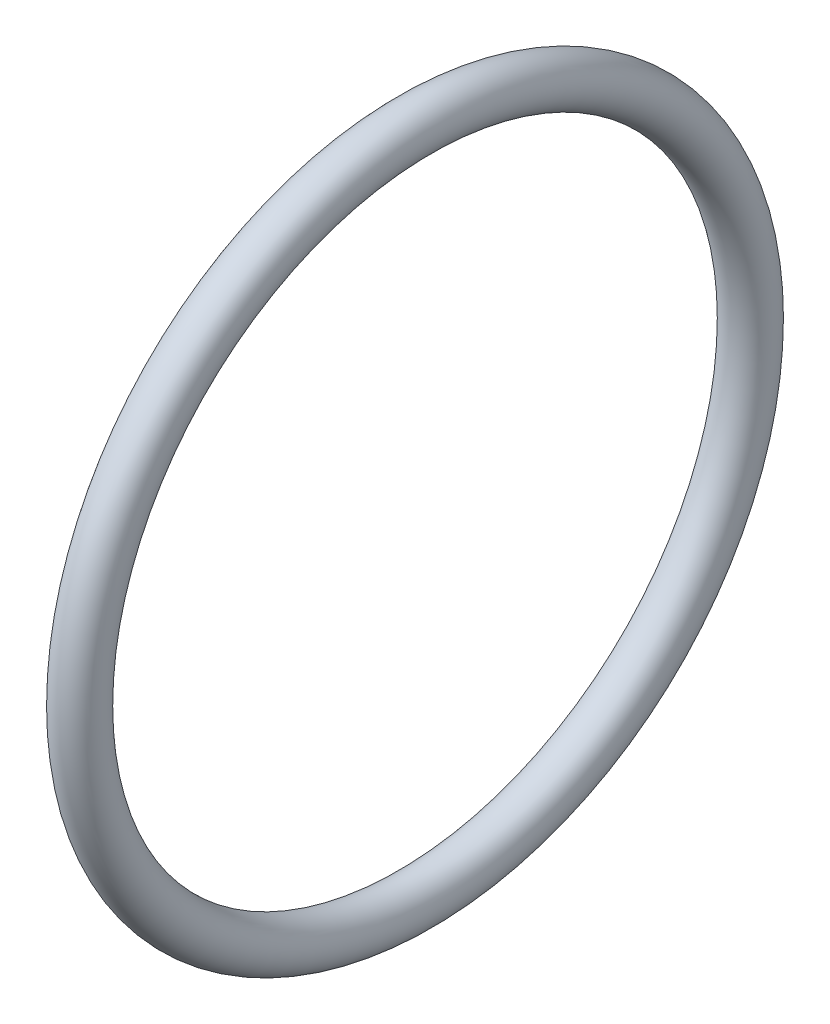
SolidWorks part; units mm, degrees
ref_plane "Front Plane" through (0, 0, 0) normal (0, 0, 1) x (1, 0, 0)
ref_plane "Top Plane" through (0, 0, 0) normal (0, 1, 0) x (1, 0, 0)
ref_plane "Right Plane" through (0, 0, 0) normal (1, 0, 0) x (0, 0, -1)
sketch "Sketch2" plane through (0, 0, 0) normal (0, 0, 1) x (1, 0, 0)
  line L0 (0, 0) -> (58.591, 0) construction
  line L2 (0, 0) -> (18.4, 0)
  line L3 (0, 0) -> (0, 2.5)
  line L4 (0, 2.5) -> (18.4, 2.5)
  line L5 (18.4, 0) -> (18.4, 2.5)
  line L6 (6.0094, 2.5) -> (6.0094, 6)
  line L11 (6.0094, 6) -> (9.9794, 6)
  line L16 (12.9794, 6) -> (12.9794, 3)
  line L17 (12.9794, 3) -> (13.6398, 3)
  line L18 (13.6398, 3) -> (13.6398, 2.5)
  line L19 (13.6398, 2.5) -> (6.0094, 2.5)
  line L22 (13.6398, 2.5) -> (16.1198, 2.5)
  line L23 (13.6398, 2.5) -> (13.6398, 4)
  line L24 (13.6398, 4) -> (16.1198, 4)
  line L25 (16.1198, 2.5) -> (16.1198, 4)
  line L27 (6.0094, 6) -> (9.9794, 6)
  line L28 (6.0094, 6) -> (6.0094, 9)
  line L29 (6.0094, 9) -> (9.9794, 9)
  line L30 (9.9794, 6) -> (9.9794, 9)
  line L31 (6.0094, 9) -> (6.0094, 8.25)
  line L32 (6.0094, 8.25) -> (5.0094, 8.25)
  line L33 (8.6609, 22.001) -> (8.6609, 12.476) construction
  line L34 (5.0094, 12.476) -> (12.3124, 12.476)
  line L35 (9.9794, 9) -> (12.3124, 9)
  line L36 (5.0094, 7.9375) -> (1.8344, 7.9375)
  line L37 (5.0094, 8.25) -> (5.0094, 12.476)
  line L38 (5.0094, 7.9375) -> (5.0094, 13.9365)
  line L39 (5.0094, 13.9365) -> (1.8344, 13.9365)
  line L40 (1.8344, 7.9375) -> (1.8344, 13.9365)
  line L41 (5.0094, 22.001) -> (12.3124, 22.001)
  line L42 (5.0094, 22.001) -> (5.0094, 30.1625)
  line L43 (5.0094, 30.1625) -> (12.3124, 30.1625)
  line L44 (12.3124, 22.001) -> (12.3124, 30.1625)
  line L49 (16.6398, 22.001) -> (16.6398, 7.5)
  line L51 (23.0198, 7.5) -> (23.0198, 6.5)
  line L54 (16.1198, 4) -> (13.6398, 4)
  line L56 (18.0398, 7.5) -> (23.0198, 7.5)
  line L57 (13.3124, 22.001) -> (16.6398, 22.001)
  line L58 (16.1198, 3.5) -> (20.0198, 3.5)
  line L59 (29.9098, 14) -> (26.9098, 11)
  line L60 (4.0094, 31.75) -> (18.0398, 31.75)
  line L61 (18.0398, 7.5) -> (23.0198, 7.5)
  line L62 (18.0398, 7.5) -> (18.0398, 12)
  line L63 (18.0398, 12) -> (23.0198, 12)
  line L64 (23.0198, 7.5) -> (23.0198, 12)
  line L65 (18.0398, 31.75) -> (18.0398, 12)
  line L66 (23.0198, 11) -> (26.9098, 11)
  line L67 (34.8098, 23) -> (31.3098, 19.5)
  line L68 (35.8098, 31) -> (38.7998, 33.99)
  line L69 (29.9098, 14) -> (29.9098, 15)
  line L70 (29.9098, 15) -> (22.9398, 15)
  line L71 (22.9398, 15) -> (21.0398, 15)
  line L72 (18.0398, 7.5) -> (16.6398, 7.5)
  line L73 (21.0398, 15) -> (21.0398, 43)
  line L74 (19.5798, 40) -> (9.6198, 40)
  line L75 (9.6198, 40) -> (4.0094, 40)
  line L76 (21.0398, 43) -> (19.5798, 43)
  line L77 (22.9398, 15) -> (29.9098, 15)
  line L78 (22.9398, 15) -> (22.9398, 21)
  line L79 (22.9398, 21) -> (29.9098, 21)
  line L80 (29.9098, 15) -> (29.9098, 21)
  line L81 (9.6198, 40) -> (19.5798, 40)
  line L82 (9.6198, 40) -> (9.6198, 50)
  line L83 (9.6198, 50) -> (19.5798, 50)
  line L84 (19.5798, 40) -> (19.5798, 50)
  line L85 (4.0094, 40) -> (4.0094, 31.75)
  line L86 (12.9794, 3) -> (12.9794, 2.5)
  line L87 (31.3098, 19.5) -> (29.9098, 19.5)
  line L88 (21.4694, 63.5) -> (21.4694, 51.308)
  line L89 (21.4694, 63.5) -> (25.9398, 63.5)
  line L90 (25.9398, 63.5) -> (25.9398, 25)
  line L91 (27.8398, 25) -> (25.9398, 25)
  line L92 (9.6198, 48) -> (8.1598, 48)
  line L93 (8.1598, 48) -> (8.1598, 53.476)
  line L94 (8.1598, 53.476) -> (19.5798, 53.476)
  line L95 (19.5798, 53.476) -> (19.5798, 50)
  line L96 (13.8698, 63.001) -> (13.8698, 53.476) construction
  line L97 (8.1598, 63.001) -> (19.5798, 63.001)
  line L98 (8.1598, 63.001) -> (8.1598, 68.2625)
  line L99 (8.1598, 68.2625) -> (19.5798, 68.2625)
  line L100 (19.5798, 63.001) -> (19.5798, 68.2625)
  line L101 (12.9794, 6) -> (11.9794, 6)
  line L102 (8.1598, 44.825) -> (4.9848, 44.825)
  line L103 (8.1598, 44.825) -> (8.1598, 54.9365)
  line L104 (8.1598, 54.9365) -> (4.9848, 54.9365)
  line L106 (9.9794, 6) -> (10.8794, 6)
  line L107 (27.8398, 25) -> (34.8098, 25)
  line L108 (34.8098, 25) -> (34.8098, 23)
  line L109 (0, 0) -> (-2, 0)
  line L110 (0, 0) -> (0, 11)
  line L111 (27.8398, 25) -> (34.8098, 25)
  line L112 (27.8398, 25) -> (27.8398, 32.5)
  line L113 (27.8398, 32.5) -> (34.8098, 32.5)
  line L114 (34.8098, 25) -> (34.8098, 32.5)
  line L115 (35.8098, 31) -> (34.8098, 31)
  line L116 (27.8398, 32.5) -> (27.8398, 64.5)
  line L117 (20.5373, 74.025) -> (6.2023, 74.025)
  line L118 (6.2023, 74.025) -> (6.2023, 76.2)
  line L119 (38.7998, 47.29) -> (30.8398, 55.25)
  line L120 (0, 11) -> (-2, 11)
  line L121 (38.7998, 43.815) -> (30.8623, 43.815)
  line L123 (-4.8152, 69.85) -> (1.5348, 76.2)
  line L124 (38.7998, 47.29) -> (38.7998, 33.99)
  line L125 (-2, 0) -> (-2, 11)
  line L126 (38.7998, 37.465) -> (30.8623, 37.465)
  line L127 (30.8623, 43.815) -> (30.8623, 37.465)
  line L128 (6.0094, 2.5) -> (6.0094, 0)
  line L129 (-0.0152, 63.5) -> (-0.0152, 30)
  line L132 (4.9848, 63.5) -> (-0.0152, 63.5)
  line L136 (-1.8152, 30) -> (-11.7752, 30)
  line L138 (-13.7752, 25.4) -> (-2, 25.4)
  line L139 (-2, 25.4) -> (-2, 11.5)
  line L140 (27.8398, 64.5) -> (20.5373, 64.5)
  line L141 (-1.8152, 30) -> (-11.7752, 30)
  line L142 (-1.8152, 30) -> (-1.8152, 39)
  line L143 (-1.8152, 39) -> (-11.7752, 39)
  line L144 (-11.7752, 30) -> (-11.7752, 39)
  line L145 (20.5373, 64.5) -> (20.5373, 74.025)
  line L146 (-12.7752, 37) -> (-12.7752, 47.29)
  line L147 (-12.7752, 37) -> (-11.7752, 37)
  line L148 (30.8398, 55.25) -> (30.8398, 76.2)
  line L149 (11.9794, 6) -> (11.9794, 5.45)
  line L154 (-2, 11.5) -> (0.5, 11.5)
  line L155 (4.9848, 60.6197) -> (24.0348, 60.6197)
  line L160 (4.9848, 60.6197) -> (4.9848, 55.8572)
  line L161 (4.9848, 55.8572) -> (24.0348, 55.8572)
  line L166 (24.0348, 60.6197) -> (24.0348, 55.8572)
  line L167 (4.9848, 60.6197) -> (24.0348, 55.8572) construction
  line L172 (4.9848, 55.8572) -> (24.0348, 60.6197) construction
  line L173 (24.0348, 62.2072) -> (25.9398, 62.2072)
  line L174 (11.9794, 5.45) -> (10.8794, 5.45)
  line L175 (10.8794, 6) -> (10.8794, 5.45)
  line L176 (24.0348, 62.2072) -> (24.0348, 54.2697)
  line L177 (24.0348, 54.2697) -> (25.9398, 54.2697)
  line L178 (25.9398, 62.2072) -> (25.9398, 54.2697)
  line L179 (24.0348, 62.2072) -> (25.9398, 54.2697) construction
  line L180 (24.0348, 54.2697) -> (25.9398, 62.2072) construction
  line L181 (3, 19.6197) -> (15.7, 19.6197)
  line L182 (3, 19.6197) -> (3, 14.8572)
  line L183 (3, 14.8572) -> (15.7, 14.8572)
  line L184 (15.7, 19.6197) -> (15.7, 14.8572)
  line L185 (3, 19.6197) -> (15.7, 14.8572) construction
  line L186 (3, 14.8572) -> (15.7, 19.6197) construction
  line L187 (15.7, 21.2072) -> (16.6398, 21.2072)
  line L188 (15.7, 21.2072) -> (15.7, 13.2697)
  line L189 (15.7, 13.2697) -> (16.6398, 13.2697)
  line L190 (16.6398, 21.2072) -> (16.6398, 13.2697)
  line L191 (15.7, 21.2072) -> (16.6398, 13.2697) construction
  line L192 (15.7, 13.2697) -> (16.6398, 21.2072) construction
  line L193 (0.5, 11.5) -> (0.5, 6.9375)
  line L194 (0.5, 6.9375) -> (1.8344, 6.9375)
  line L195 (23.0198, 6.5) -> (20.0198, 3.5)
  line L196 (4.9848, 63.5) -> (4.9848, 54.9365)
  line L197 (3, 43.825) -> (4.9848, 43.825)
  line L198 (1.8344, 6.9375) -> (1.8344, 7.9375)
  line L199 (6.0094, 0) -> (12.9794, 0)
  line L200 (12.9794, 0) -> (12.9794, 2.5)
  line L201 (18.0398, 31.75) -> (18.0398, 35.875)
  line L202 (18.0398, 35.875) -> (21.0398, 35.875)
  line L203 (30.8398, 76.2) -> (6.2023, 76.2)
  line L204 (2.7573, 69.85) -> (7.2023, 69.85) construction
  line L205 (7.2023, 67.4688) -> (26.2523, 67.4688)
  line L206 (7.2023, 74.025) -> (7.2023, 64.5)
  line L207 (7.2023, 64.5) -> (-1.8152, 64.5)
  line L208 (-1.8152, 64.5) -> (-1.8152, 39)
  line L209 (-12.7752, 47.29) -> (-4.8152, 55.25)
  line L210 (-4.8152, 55.25) -> (-4.8152, 69.85)
  line L211 (7.2023, 67.4688) -> (7.2023, 72.2312)
  line L212 (7.2023, 72.2312) -> (26.2523, 72.2313)
  line L213 (26.2523, 67.4688) -> (26.2523, 72.2313)
  line L214 (26.2523, 73.8187) -> (30.8398, 73.8187)
  line L215 (26.2523, 73.8187) -> (26.2523, 65.8813)
  line L216 (26.2523, 65.8813) -> (30.8398, 65.8813)
  line L217 (30.8398, 73.8187) -> (30.8398, 65.8813)
  line L218 (2.7573, 72.2313) -> (24.9823, 72.2313)
  line L219 (2.7573, 72.2313) -> (2.7573, 67.4687)
  line L220 (2.7573, 67.4687) -> (24.9823, 67.4687)
  line L221 (24.9823, 72.2313) -> (24.9823, 67.4687)
  line L222 (24.9823, 69.85) -> (20.5373, 69.85) construction
  line L223 (21.4694, 51.308) -> (22.9398, 51.308)
  line L224 (22.9398, 51.308) -> (22.9398, 21)
  line L225 (13.6398, 4) -> (13.6398, 12.2697)
  line L226 (13.6398, 12.2697) -> (13.3124, 12.2697)
  line L227 (13.3124, 12.2697) -> (13.3124, 22.001)
  line L228 (12.3124, 9) -> (12.3124, 12.476)
  line L229 (-1.8152, 30) -> (-0.0152, 30)
  line L230 (8.1598, 65.6317) -> (2.7573, 65.6317) construction
  line L231 (19.5798, 65.6317) -> (24.9823, 65.6317) construction
  line L232 (1.5348, 76.2) -> (6.2023, 76.2)
  line L233 (-11.7752, 30) -> (-13.7752, 30)
  line L234 (-13.7752, 30) -> (-13.7752, 25.4)
  line L235 (3, 13.9365) -> (3, 43.825)
  line L236 (4.9848, 54.9365) -> (4.9848, 44.825)
  line L237 (4.9848, 43.825) -> (4.9848, 44.825)
  circle A0 centre (26.8898, 25.95) radius 0.95
  circle A1 centre (21.9898, 15.95) radius 0.95
  circle A2 centre (17.3398, 8.2) radius 0.7
  circle A3 centre (10.4294, 6.45) radius 0.45
  circle A4 centre (-0.9152, 30.9) radius 0.9
  point P7 (24.9873, 58.2385)
  point P131 (16.1699, 17.2385)
  point P135 (14.5098, 58.2385)
  point P146 (9.35, 17.2385)
sketch "Sketch3" plane through (0, 0, 0) normal (0, 0, 1) x (1, 0, 0)
  circle A0 centre (10.4294, 6.45) radius 0.45 construction
  circle A1 centre (10.4294, 6.45) radius 0.45
revolve "Revolve1" add sketch "Sketch3" angle 360 about L0
